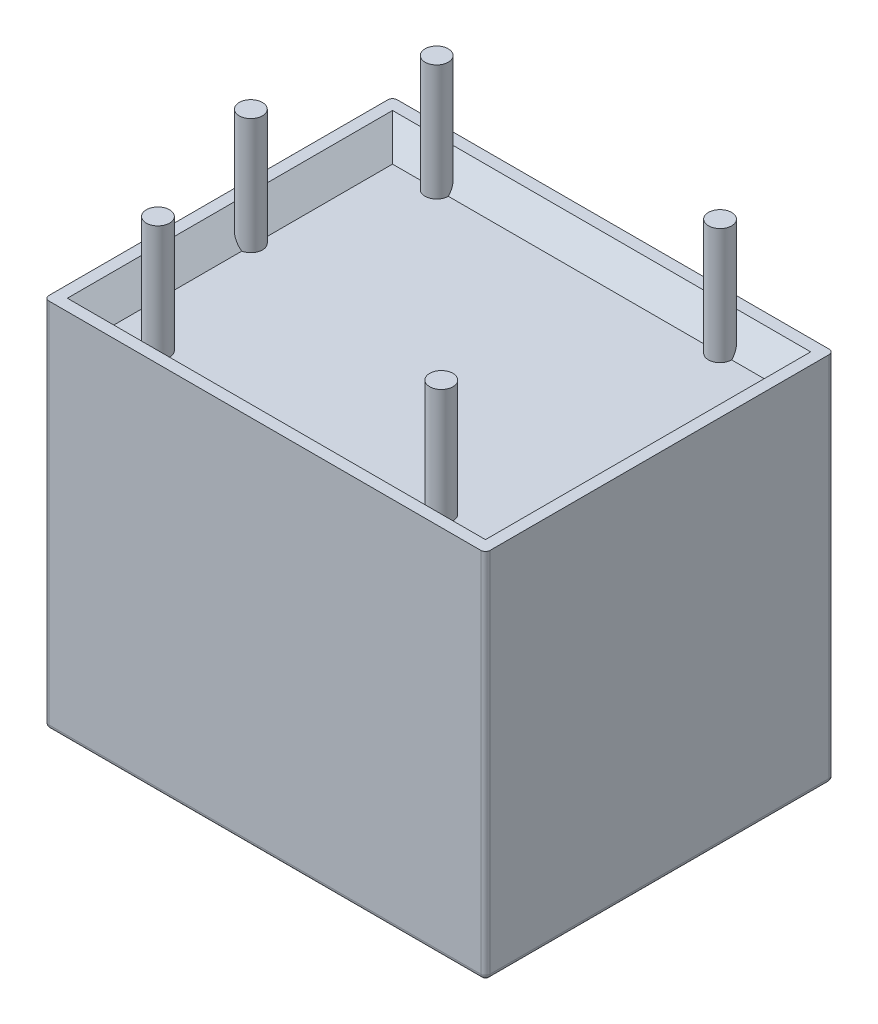
SolidWorks part; units mm, degrees
ref_plane "Front Plane" through (0, 0, 0) normal (0, 0, 1) x (1, 0, 0)
ref_plane "Top Plane" through (0, 0, 0) normal (0, 1, 0) x (1, 0, 0)
ref_plane "Right Plane" through (0, 0, 0) normal (1, 0, 0) x (0, 0, -1)
sketch "Sketch2" plane through (0, 0, 0) normal (0, 1, 0) x (1, 0, 0)
  line L1 (-9.5, -7.5) -> (9.5, -7.5)
  line L2 (-9.5, -7.5) -> (-9.5, 7.5)
  line L3 (-9.5, 7.5) -> (9.5, 7.5)
  line L4 (9.5, -7.5) -> (9.5, 7.5)
  line L5 (-9.5, -7.5) -> (9.5, 7.5) construction
  line L6 (-9.5, 7.5) -> (9.5, -7.5) construction
  point P0 (0, 0)
  dimension "D1" = 19
  dimension "D2" = 15
extrude "Boss-Extrude1" add sketch "Sketch2" along normal blind 16
sketch "Sketch3" plane through (0, 16, 0) normal (0, 1, 0) x (1, 0, 0)
  line L1 (-9, 7) -> (9, 7)
  line L2 (-9, 7) -> (-9, -7)
  line L3 (-9, -7) -> (9, -7)
  line L4 (9, 7) -> (9, -7)
  line L5 (-9, 7) -> (9, -7) construction
  line L6 (-9, -7) -> (9, 7) construction
  point P0 (0, 0)
  dimension "D1" = 18
  dimension "D2" = 14
extrude "Cut-Extrude1" cut sketch "Sketch3" against normal blind 1
chamfer "Chamfer1" distance 1 angle 45 4 edges at (0, 15, 7) (9, 15, 0) (0, 15, -7) (-9, 15, 0)
sketch "Sketch4" plane through (0, 15, 0) normal (0, 1, 0) x (1, 0, 0)
  line L0 (-9.5, 7.5) -> (-9.5, -7.5) construction
  line L1 (9.5, -7.5) -> (9.5, 7.5) construction
  circle A0 centre (-8.1, 0) radius 0.5
  circle A1 centre (-6.1, 6) radius 0.5
  circle A2 centre (6.1, 6) radius 0.5
  dimension "D2" = 6
  dimension "D4" = 3.4
  dimension "D1" = 1.4
  dimension "D3" = 2
extrude "Boss-Extrude3" add sketch "Sketch4" along normal blind 5
mirror "Mirror1" about plane through (0, 0, 0) normal (0, 0, 1) of "Boss-Extrude3"
fillet "Fillet1" radius 0.2 8 edges at (9.5, 8, 7.5) (9.5, 8, -7.5) (-9.5, 8, 7.5) (-9.5, 8, -7.5) (0, 0, 7.5) (9.5, 0, 0) (0, 0, -7.5) (-9.5, 0, 0)
